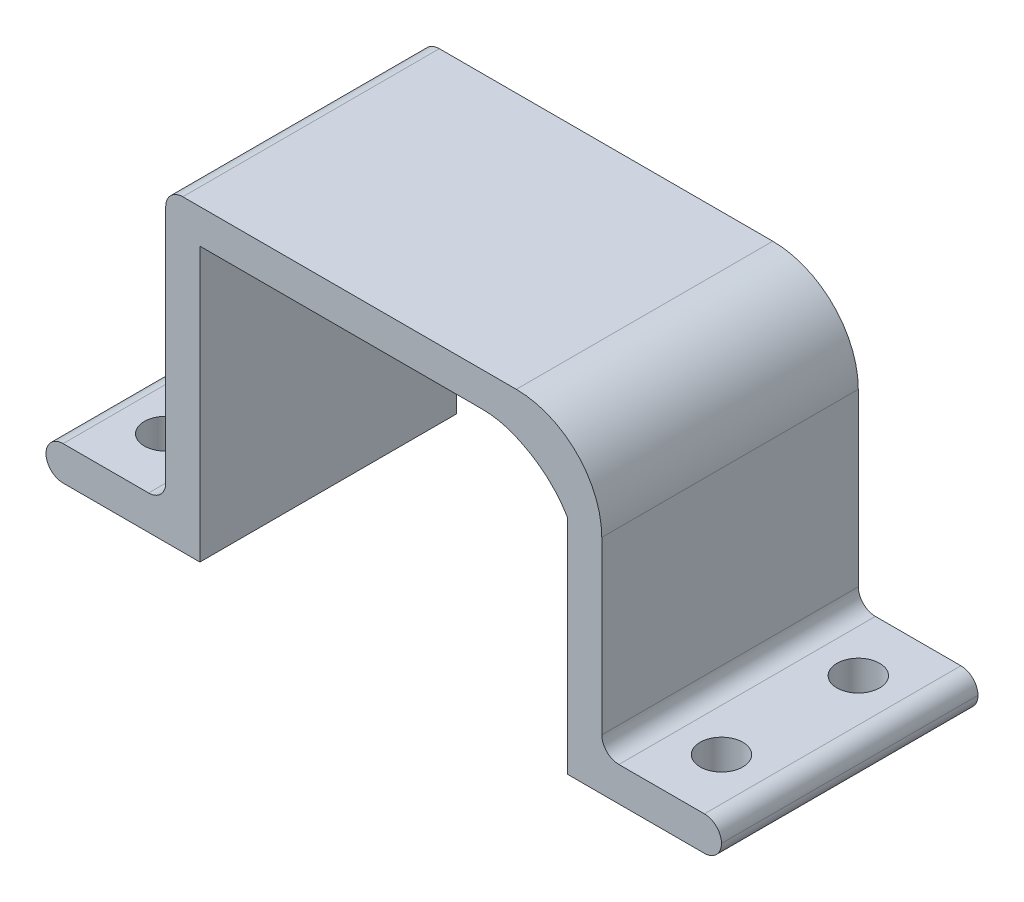
SolidWorks part; units mm, degrees
ref_plane "Front Plane" through (0, 0, 0) normal (0, 0, 1) x (1, 0, 0)
ref_plane "Top Plane" through (0, 0, 0) normal (0, 1, 0) x (1, 0, 0)
ref_plane "Right Plane" through (0, 0, 0) normal (1, 0, 0) x (0, 0, -1)
sketch "Sketch1" plane through (0, 0, 0) normal (0, 0, 1) x (1, 0, 0)
  line L0 (0, 0) -> (18, 0)
  line L1 (18, 0) -> (18, 32)
  line L2 (18, 32) -> (51, 32)
  line L3 (61, 22) -> (61, 0)
  line L4 (61, 0) -> (79, 0)
  line L5 (0, 4) -> (14, 4)
  line L6 (14, 4) -> (14, 36)
  line L7 (14, 36) -> (55, 36)
  line L8 (65, 26) -> (65, 4)
  line L9 (65, 4) -> (79, 4)
  line L10 (0, 0) -> (0, 4)
  line L11 (79, 0) -> (79, 4)
  line L12 (18, 32) -> (61, 32) construction
  line L13 (61, 32) -> (61, 0) construction
  line L14 (65, 36) -> (65, 4) construction
  line L15 (14, 36) -> (65, 36) construction
  arc A0 (51, 32) -> (61, 22) centre (51, 22) cw
  arc A1 (65, 26) -> (55, 36) centre (55, 26) ccw
  point P17 (61, 32)
  dimension "D5" = 10
  dimension "D6" = 10
  dimension "D1" = 32
  dimension "D2" = 43
  dimension "D3" = 18
  dimension "D4" = 4
extrude "Boss-Extrude1" add sketch "Sketch1" along normal blind 30
sketch "Sketch2" plane through (0, 4, 0) normal (0, 1, 0) x (1, 0, 0)
  line L0 (14, 0) -> (0, 0) construction
  line L1 (14, -30) -> (0, -30) construction
  line L2 (79, -30) -> (65, -30) construction
  line L4 (79, 0) -> (65, 0) construction
  circle A0 centre (7, -7) radius 2.5
  circle A1 centre (7, -23) radius 2.5
  circle A2 centre (72, -7) radius 2.5
  circle A3 centre (72, -23) radius 2.5
  point P6 (7, 0)
  point P15 (72, -30)
  dimension "D2" = 5
  dimension "D4" = 5
  dimension "D1" = 7
  dimension "D3" = 7
  dimension "D5" = 7
  dimension "D6" = 7
extrude "Cut-Extrude1" cut sketch "Sketch2" against normal through all
sketch "Sketch3" plane through (0, 0, 30) normal (0, 0, 1) x (1, 0, 0)
  line L0 (61, 22) -> (61, 26.0076)
  arc A0 (61, 26.0076) -> (51, 32) centre (50.4101, 19.6754) ccw
  arc A1 (61, 22) -> (51, 32) centre (51, 22) ccw
  arc M5 (51, 32) -> (61, 22) centre (51, 22) cw
extrude "Cut-Extrude2" cut sketch "Sketch3" against normal through all contours L0 A0 M5 region at (59.8623, 26.7528, 30)
fillet "Fillet1" radius 2 7 edges at (79, 0, 15) (79, 4, 15) (65, 4, 15) (14, 36, 15) (0, 0, 15) (0, 4, 15) (14, 4, 15)
